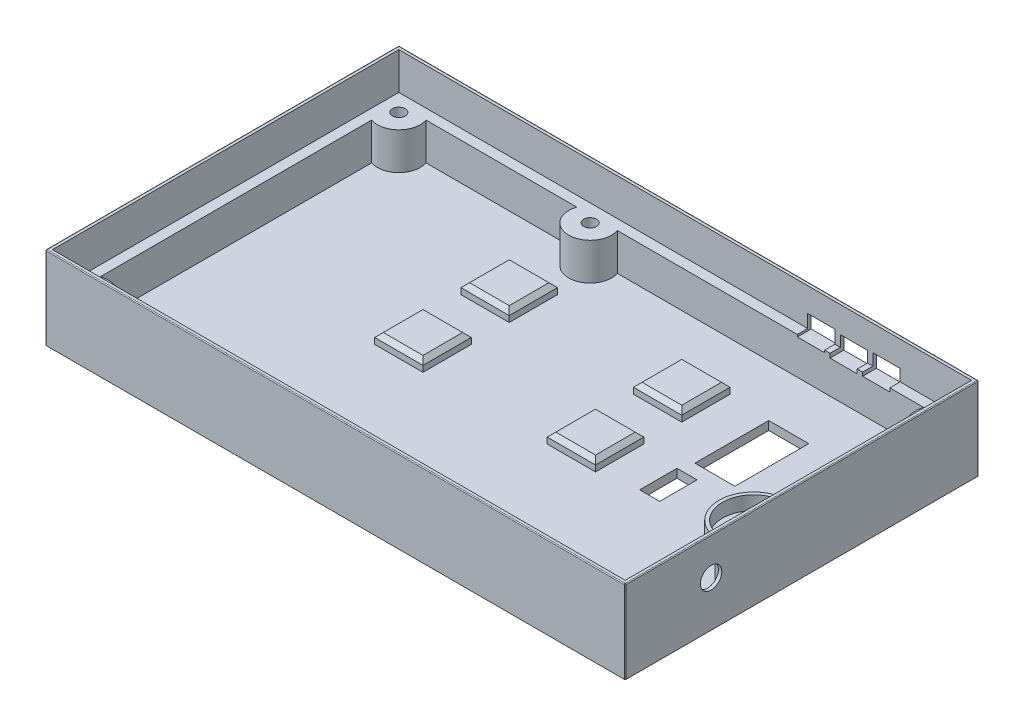
SolidWorks part; units mm, degrees
ref_plane "Front Plane" through (0, 0, 0) normal (0, 0, 1) x (1, 0, 0)
ref_plane "Top Plane" through (0, 0, 0) normal (0, 1, 0) x (1, 0, 0)
ref_plane "Right Plane" through (0, 0, 0) normal (1, 0, 0) x (0, 0, -1)
sketch "BaseSketch1" plane through (0, 0, 0) normal (0, 1, 0) x (1, 0, 0)
  line L1 (0, 0) -> (168, 0)
  line L2 (0, 0) -> (0, 102.4)
  line L3 (0, 102.4) -> (168, 102.4)
  line L4 (168, 0) -> (168, 102.4)
  line L5 (126.2, 83.4) -> (137.8, 83.4)
  line L6 (126.2, 83.4) -> (126.2, 62)
  line L7 (126.2, 62) -> (137.8, 62)
  line L8 (137.8, 83.4) -> (137.8, 62)
  line L9 (124.9, 47.31) -> (130.7, 47.31)
  line L10 (124.9, 47.31) -> (124.9, 58.11)
  line L11 (124.9, 58.11) -> (130.7, 58.11)
  line L12 (130.7, 47.31) -> (130.7, 58.11)
  circle A0 centre (57, 77.4) radius 2
  circle A1 centre (107, 77.4) radius 2
  circle A2 centre (57, 52.4) radius 2
  circle A3 centre (107, 52.4) radius 2
  circle A4 centre (6, 96.4) radius 1.85
  circle A5 centre (6, 6) radius 1.85
  circle A6 centre (162, 6) radius 1.85
  circle A7 centre (162, 96.4) radius 1.85
  circle A8 centre (61.45, 96.4) radius 1.85
  dimension "D16" = 3.7
  dimension "D7" = 4
  dimension "D1" = 102.4
  dimension "D2" = 168
  dimension "D3" = 50
  dimension "D4" = 25
  dimension "D6" = 25
  dimension "D8" = 21.4
  dimension "D9" = 11.6
  dimension "D10" = 40.4
  dimension "D12" = 5.8
  dimension "D13" = 10.8
  dimension "D15" = 55.09
  dimension "D17" = 6
  dimension "D18" = 6
  dimension "D19" = 6
  dimension "D20" = 6
  dimension "D5" = 57
  dimension "D11" = 41.8
  dimension "D14" = 43.1
  dimension "D21" = 106.55
extrude "BaseBoss-Extrude1" add sketch "BaseSketch1" along normal blind 2.5
sketch "Sketch2" plane through (0, 2.5, 0) normal (0, 1, 0) x (1, 0, 0)
  line L1 (0, 0) -> (168, 0)
  line L2 (0, 0) -> (0, 102.4)
  line L3 (0, 102.4) -> (168, 102.4)
  line L4 (168, 0) -> (168, 102.4)
  line L5 (4, 98.4) -> (164, 98.4)
  line L6 (4, 98.4) -> (4, 4)
  line L7 (4, 4) -> (164, 4)
  line L8 (164, 98.4) -> (164, 4)
  dimension "D1" = 4
  dimension "D2" = 4
  dimension "D3" = 4
  dimension "D4" = 4
extrude "WallBoss-Extrude2" add sketch "Sketch2" along normal blind 21.5
sketch "Sketch3" plane through (0, 2.5, 0) normal (0, 1, 0) x (1, 0, 0)
  line L1 (50, 84.4) -> (64, 84.4)
  line L2 (50, 84.4) -> (50, 70.4)
  line L3 (50, 70.4) -> (64, 70.4)
  line L4 (64, 84.4) -> (64, 70.4)
  line L5 (50, 84.4) -> (64, 70.4) construction
  line L6 (50, 70.4) -> (64, 84.4) construction
  line L7 (50, 59.4) -> (64, 59.4)
  line L8 (50, 59.4) -> (50, 45.4)
  line L9 (50, 45.4) -> (64, 45.4)
  line L10 (64, 59.4) -> (64, 45.4)
  line L11 (50, 59.4) -> (64, 45.4) construction
  line L12 (50, 45.4) -> (64, 59.4) construction
  line L13 (100, 84.4) -> (114, 84.4)
  line L14 (100, 84.4) -> (100, 70.4)
  line L15 (100, 70.4) -> (114, 70.4)
  line L16 (114, 84.4) -> (114, 70.4)
  line L17 (100, 84.4) -> (114, 70.4) construction
  line L18 (100, 70.4) -> (114, 84.4) construction
  line L19 (100, 59.4) -> (114, 59.4)
  line L20 (100, 59.4) -> (100, 45.4)
  line L21 (100, 45.4) -> (114, 45.4)
  line L22 (114, 59.4) -> (114, 45.4)
  line L23 (100, 59.4) -> (114, 45.4) construction
  line L24 (100, 45.4) -> (114, 59.4) construction
  point P0 (57, 77.4)
  point P6 (57, 52.4)
  point P12 (107, 77.4)
  point P18 (107, 52.4)
  dimension "D1" = 14
extrude "MountHoleBoss-Extrude3" add sketch "Sketch3" along normal blind 3
chamfer "MountHoleBossChamfer3" distance 1.25 angle 45 16 edges at (57, 5.5, -59.4) (107, 5.5, -59.4) (107, 5.5, -84.4) (57, 5.5, -84.4) (50, 5.5, -52.4) (100, 5.5, -52.4) (100, 5.5, -77.4) (50, 5.5, -77.4) (64, 5.5, -52.4) (114, 5.5, -52.4) (114, 5.5, -77.4) (64, 5.5, -77.4) (57, 5.5, -70.4) (57, 5.5, -45.4) (107, 5.5, -45.4) (107, 5.5, -70.4)
sketch "HDMI7MountHolesSketch8" plane through (0, 2.5, 0) normal (0, 1, 0) x (1, 0, 0)
  line L0 (164, 98.4) -> (4, 98.4) construction
  line L1 (4, 98.4) -> (4, 4) construction
  line L2 (4, 90.5243) -> (4, 98.4)
  line L3 (4, 98.4) -> (11.8757, 98.4)
  line L4 (164, 4) -> (164, 98.4) construction
  line L5 (4, 4) -> (164, 4) construction
  line L6 (4, 98.4) -> (4, 4) construction
  line L7 (4, 4) -> (164, 4) construction
  line L8 (156.1243, 98.4) -> (164, 98.4)
  line L9 (164, 98.4) -> (164, 90.5243)
  line L10 (156.1243, 4) -> (164, 4)
  line L11 (164, 4) -> (164, 11.8757)
  line L12 (11.8757, 4) -> (4, 4)
  line L13 (4, 4) -> (4, 11.8757)
  line L14 (55.5743, 98.4) -> (67.3257, 98.4)
  arc A0 (11.8757, 98.4) -> (4, 90.5243) centre (6, 96.4) cw
  circle A1 centre (6, 96.4) radius 1.85
  circle A2 centre (6, 96.4) radius 1.85 construction
  circle A3 centre (162, 96.4) radius 1.85
  circle A4 centre (162, 96.4) radius 1.85 construction
  arc A5 (164, 90.5243) -> (156.1243, 98.4) centre (162, 96.4) cw
  arc A6 (164, 11.8757) -> (156.1243, 4) centre (162, 6) ccw
  arc A7 (4, 11.8757) -> (11.8757, 4) centre (6, 6) cw
  circle A8 centre (162, 6) radius 1.85
  circle A9 centre (162, 6) radius 1.85 construction
  circle A10 centre (6, 6) radius 1.85
  circle A11 centre (6, 6) radius 1.85 construction
  arc A12 (55.5743, 98.4) -> (67.3257, 98.4) centre (61.45, 96.4) ccw
  circle A13 centre (61.45, 96.4) radius 1.85
  circle A14 centre (61.45, 96.4) radius 1.85 construction
extrude "HDMI7MountHolesBoss-Extrude4" add sketch "HDMI7MountHolesSketch8" along normal blind 10.75
sketch "DisplayButtonsSketch9" plane through (0, 0, -102.4) normal (0, 0, -1) x (-1, 0, 0)
  line L0 (-168, 24) -> (0, 24) construction
  line L1 (-146.3, 16.61) -> (-138.4, 16.61)
  line L2 (-146.3, 16.61) -> (-146.3, 12.21)
  line L3 (-146.3, 12.21) -> (-138.4, 12.21)
  line L4 (-138.4, 16.61) -> (-138.4, 12.21)
  line L5 (-136.85, 16.4439) -> (-128.95, 16.4439)
  line L6 (-136.85, 16.4439) -> (-136.85, 12.0439)
  line L7 (-136.85, 12.0439) -> (-128.95, 12.0439)
  line L8 (-128.95, 16.4439) -> (-128.95, 12.0439)
  line L9 (-127.4, 17.0239) -> (-119.5, 17.0239)
  line L10 (-127.4, 17.0239) -> (-127.4, 12.6239)
  line L11 (-127.4, 12.6239) -> (-119.5, 12.6239)
  line L12 (-119.5, 17.0239) -> (-119.5, 12.6239)
  line L13 (-168, 24) -> (-168, 0) construction
  dimension "D1" = 7.9
  dimension "D3" = 11.79
  dimension "D4" = 29.6
  dimension "D2" = 4.4
  dimension "D6" = 1.55
  dimension "D5" = 1.55
  dimension "D7" = 48.5
  dimension "D8" = 7.9
  dimension "D9" = 7.9
extrude "DisplayButtonsCut-Extrude1" cut sketch "DisplayButtonsSketch9" against normal up to next
sketch "AudioConnectorSketch10" plane through (168, 0, 0) normal (1, 0, 0) x (0, 0, -1)
  line L0 (0, 24) -> (102.4, 24) construction
  line L1 (0, 24) -> (0, 0) construction
  circle A0 centre (24.9, 13.2) radius 3.1
  dimension "D1" = 6.2
  dimension "D2" = 10.8
  dimension "D3" = 24.9
extrude "AudioConnectorCut-Extrude2" cut sketch "AudioConnectorSketch10" against normal up to next
sketch "M3BoreSketch11" plane through (0, 0, 0) normal (0, -1, 0) x (1, 0, 0)
  circle A0 centre (6, -6) radius 2.85
  circle A1 centre (162, -6) radius 2.85
  circle A2 centre (162, -96.4) radius 2.85
  circle A3 centre (6, -96.4) radius 2.85
  circle A4 centre (61.45, -96.4) radius 2.85
  dimension "D1" = 5.7
extrude "M3BoreCut-Extrude3" cut sketch "M3BoreSketch11" against normal blind 3
sketch "UpperThinWallSketch4" plane through (0, 24, 0) normal (0, 1, 0) x (1, 0, 0)
  line L1 (4, 98.4) -> (164, 98.4)
  line L2 (4, 98.4) -> (4, 4)
  line L3 (4, 4) -> (164, 4)
  line L4 (164, 98.4) -> (164, 4)
  line L6 (167, 1) -> (1, 1)
  line L7 (167, 1) -> (167, 101.4)
  line L8 (167, 101.4) -> (1, 101.4)
  line L9 (1, 1) -> (1, 101.4)
  dimension "D1" = 3
  dimension "D2" = 3
  dimension "D3" = 3
  dimension "D4" = 3
extrude "UpperThinWallCut-Extrude1" cut sketch "UpperThinWallSketch4" against normal blind 10.75
sketch "HDMI7AudioConnectorKnotchSketch5" plane through (0, 13.25, 0) normal (0, 1, 0) x (1, 0, 0)
  line L0 (164, 27.9996) -> (167, 27.9996) construction
  line L1 (164, 29.9996) -> (167, 29.9996)
  line L2 (164, 29.9996) -> (164, 19.8004)
  line L3 (164, 19.8004) -> (167, 19.8004)
  line L4 (167, 29.9996) -> (167, 19.8004)
  line L6 (167, 1) -> (167, 21.8004) construction
  line L7 (164, 11.8757) -> (164, 90.5243) construction
  line L8 (167, 21.8004) -> (164, 21.8004) construction
  dimension "D1" = 2
  dimension "D2" = 2
extrude "HDMI7AudioConnectorKnotchCut-Extrude2" cut sketch "HDMI7AudioConnectorKnotchSketch5" against normal blind 8.2
fillet "TopFillet1" radius 0.25 4 edges at (168, 24, -51.2) (84, 24, 0) (0, 24, -51.2) (84, 24, -102.4)
fillet "CornerFillet2" radius 0.25 8 edges at (0.0732, 23.9268, -0.0732) (0.0732, 23.9268, -102.3268) (167.9268, 23.9268, -0.0732) (0, 11.875, 0) (0, 11.875, -102.4) (168, 11.875, 0) (167.9268, 23.9268, -102.3268) (168, 11.875, -102.4)
sketch "SpeakerHoleSketch4" plane through (0, 2.5, 0) normal (0, 1, 0) x (1, 0, 0)
  line L0 (0.25, 102.4) -> (167.75, 102.4) construction
  line L1 (168, 102.15) -> (168, 0.25) construction
  circle A0 centre (153, 52.2) radius 6.75
  dimension "D1" = 13.5
  dimension "D2" = 50.2
  dimension "D3" = 15
extrude "SpeaerHoleCut-Extrude1" cut sketch "SpeakerHoleSketch4" against normal through all
sketch "SpeakerHolderSketch5" plane through (0, 2.5, 0) normal (0, 1, 0) x (1, 0, 0)
  line L2 (50, 59.4) -> (50, 45.4) construction
  line L3 (50, 45.4) -> (64, 45.4) construction
  circle A0 centre (153, 52.2) radius 9
  circle A1 centre (153, 52.2) radius 10
  point P4 (0, 0)
  point P12 (153.2499, 42.2)
  point P13 (153.2517, 43.2)
  dimension "D1" = 18
  dimension "D2" = 20
extrude "SpeakerHolderBoss-Extrude1" add sketch "SpeakerHolderSketch5" along normal blind 4
equation "\"HDMI7CaseWidth\"= 100mm + .4mm'Spec Add .4mm as width was slightly to tight"
equation "\"D1@BaseSketch1\" = \"HDMI7CaseWidth\" + \"HDMI7OuterCaseWallThickness\" * 2"
equation "\"HDMI7CaseLength\"= 165mm + 1mm'Spec Add 1mm as length did not fit"
equation "\"HDMI7CaseHeight\"= 24mm"
equation "\"HDMI7Height\"= 10.75mm'Spec"
equation "\"HDMI7MountingHoleOffset\"= 5mm'Spec"
equation "\"M3ScrewDiameter\"= 3mm + .5'Spec Add .5mm for easy screw insert"
equation "\"D2@BaseSketch1\"= \"HDMI7CaseLength\" + \"HDMI7OuterCaseWallThickness\" * 2"
equation "\"HDMI7BaseThickness\"= 2.5mm"
equation "\"HDMIMountHoleXDistance\"=50"
equation "\"D3@BaseSketch1\"=\"HDMIMountHoleXDistance\""
equation "\"HDMIMountHoleYDistance\"=25"
equation "\"D10@BaseSketch1\"=\"HDMI7HDMIConnectorDistanceFromTop\" + \"HDMI7OuterCaseWallThickness\" + \"HDMI7SpaceAroundAConnector\""
equation "\"D6@BaseSketch1\" = \"HDMI7MountingBracketOffsetFromTop\" + \"HDMI7OuterCaseWallThickness\""
equation "\"D15@BaseSketch1\"=\"HDMI7USBCConnectorDistanceFromTop\" + \"HDMI7OuterCaseWallThickness\" + \"HDMI7SpaceAroundAConnector\"*2"
equation "\"D1@BaseBoss-Extrude1\" = \"HDMI7BaseThickness\""
equation "\"D1@Sketch2\"=\"HDMI7OuterCaseWallThickness\" + \"HDMI7InnerCaseWallThickness\""
equation "\"D2@Sketch2\"=\"HDMI7OuterCaseWallThickness\" + \"HDMI7InnerCaseWallThickness\""
equation "\"D3@Sketch2\"=\"HDMI7OuterCaseWallThickness\" +\"HDMI7InnerCaseWallThickness\""
equation "\"D4@Sketch2\"=\"HDMI7OuterCaseWallThickness\" + \"HDMI7InnerCaseWallThickness\""
equation "\"D1@WallBoss-Extrude2\" = \"HDMI7CaseHeight\" - \"HDMI7BaseThickness\""
equation "\"D1@Sketch3\"=\"M3ScrewDiameter\"*4"
equation "\"D1@MountHoleBoss-Extrude3\"=\"M3ButtonHeadLength\""
equation "\"D16@BaseSketch1\"=\"M3ScrewDiameter\" +.2"
equation "\"D18@BaseSketch1\"=\"HDMI7MountingHoleOffset\" + \"HDMI7OuterCaseWallThickness\""
equation "\"D17@BaseSketch1\"=\"HDMI7MountingHoleOffset\"+\"HDMI7OuterCaseWallThickness\""
equation "\"D19@BaseSketch1\"=\"HDMI7MountingHoleOffset\"+\"HDMI7OuterCaseWallThickness\""
equation "\"D20@BaseSketch1\"=\"HDMI7MountingHoleOffset\"+\"HDMI7OuterCaseWallThickness\""
equation "\"D1@HDMI7MountHolesBoss-Extrude4\"=\"HDMI7CaseHeight\" - \"HDMI7Height\" - \"HDMI7BaseThickness\""
equation "\"D5@BaseSketch1\" = \"HDMI7MountingBracketOffsetFromEdge\" + \"HDMI7OuterCaseWallThickness\""
equation "\"D4@DisplayButtonsSketch9\"=\"HDMI7DisplayButtonDistanceFromNearestEdge\" + \"HDMI7OuterCaseWallThickness\" + \"HDMI7SpaceAroundAConnector\""
equation "\"D2@AudioConnectorSketch10\"= \"HDMI7AudioConnectorDistanceFromTop\" - \"HDMI7AudioConnectorHoleDiameter\" / 2"
equation "\"D3@AudioConnectorSketch10\"= \"HDMI7AudioConnectorDistanceFromNearestEdge\" + \"HDMI7OuterCaseWallThickness\" - \"HDMI7AudioConnectorHoleDiameter\" / 2"
equation "\"M3ButtonHeadDiameter\"= 5.5mm'Spec"
equation "\"M3ButtonHeadLength\"= 3mm'Spec"
equation "\"D1@M3BoreSketch11\"=\"M3ButtonHeadDiameter\" + .2mm"
equation "\"D1@M3BoreCut-Extrude3\"=\"M3ButtonHeadLength\""
equation "\"HDMI7InnerCaseWallThickness\"= 3mm"
equation "\"HDMI7OuterCaseWallThickness\"= 1mm"
equation "\"D1@UpperThinWallSketch4\" = \"HDMI7InnerCaseWallThickness\""
equation "\"D2@UpperThinWallSketch4\" = \"HDMI7InnerCaseWallThickness\""
equation "\"D3@UpperThinWallSketch4\" = \"HDMI7InnerCaseWallThickness\""
equation "\"D4@UpperThinWallSketch4\" = \"HDMI7InnerCaseWallThickness\""
equation "\"D1@UpperThinWallCut-Extrude1\" = \"HDMI7Height\""
equation "\"HDMI7AudioConnectorHoleDiameter\"= 6mm + \"HDMI7SpaceAroundAConnector\" * 2"
equation "\"D1@AudioConnectorSketch10\"=\"HDMI7AudioConnectorHoleDiameter\""
equation "\"HDMI7AudioConnectorDistanceFromNearestEdge\"= 27mm"
equation "\"HDMI7AudioConnectorDistanceFromTop\"= 13.8mm + \"HDMI7SpaceAroundAConnector\""
equation "\"D1@HDMI7AudioConnectorKnotchCut-Extrude2\"=\"HDMI7AudioConnectorHoleDiameter\" + 2mm"
equation "\"HDMI7DisplayButtonDistanceFromTop\"=11.69"
equation "\"D3@DisplayButtonsSketch9\"=\"HDMI7DisplayButtonDistanceFromTop\" + \"HDMI7SpaceAroundAConnector\""
equation "\"HDMI7DisplayButtonHeight\"= 4.2mm"
equation "\"D2@DisplayButtonsSketch9\"=\"HDMI7DisplayButtonHeight\" + \"HDMI7SpaceAroundAConnector\"*2"
equation "\"HDMI7DisplayButtonWidth\"= 7.7mm"
equation "\"D1@DisplayButtonsSketch9\"=\"HDMI7DisplayButtonWidth\" + \"HDMI7SpaceAroundAConnector\" * 2"
equation "\"HDMI7DisplayButtonDistanceFromNearestEdge\"= 28.5mm"
equation "\"HDMI7DisplayButtonOffsetBetweenEach\"=1.75"
equation "\"D6@DisplayButtonsSketch9\"=\"HDMI7DisplayButtonOffsetBetweenEach\" - \"HDMI7SpaceAroundAConnector\"*2"
equation "\"D5@DisplayButtonsSketch9\"=\"HDMI7DisplayButtonOffsetBetweenEach\" - \"HDMI7SpaceAroundAConnector\"*2"
equation "\"HDMI7HDMIConnectorLength\"= 21.2mm'Measured"
equation "\"D8@BaseSketch1\"=\"HDMI7HDMIConnectorLength\" + \"HDMI7SpaceAroundAConnector\"*2"
equation "\"HDMI7HDMIConnectorWidth\"= 11.5mm'Measured"
equation "\"D9@BaseSketch1\"=\"HDMI7HDMIConnectorWidth\" + \"HDMI7SpaceAroundAConnector\""
equation "\"HDMI7USBConnectorLength\"= 10.7mm'Measured"
equation "\"D13@BaseSketch1\"=\"HDMI7USBConnectorLength\" + \"HDMI7SpaceAroundAConnector\""
equation "\"HDMI7USBCConnectorWidth\"= 5.7mm'Measured"
equation "\"D12@BaseSketch1\"=\"HDMI7USBCConnectorWidth\" + \"HDMI7SpaceAroundAConnector\""
equation "\"HDMI7HDMIConnectorDistanceFromNearestSide\"= 38.7mm"
equation "\"HDMI7USBConnectorDistanceFromNearestSide\" = 40mm"
equation "\"D11@BaseSketch1\"=\"HDMI7HDMIConnectorDistanceFromNearestSide\" + \"HDMI7InnerCaseWallThickness\" + \"HDMI7SpaceAroundAConnector\""
equation "\"D14@BaseSketch1\"=\"HDMI7USBConnectorDistanceFromNearestSide\" +\"HDMI7InnerCaseWallThickness\" + \"HDMI7SpaceAroundAConnector\""
equation "\"HDMI7USBCConnectorDistanceFromTop\" = 53.89mm"
equation "\"HDMI7HDMIConnectorDistanceFromTop\"= 39.3mm"
equation "\"HDMI7MountingBracketOffsetFromEdge\"= 56mm"
equation "\"HDMI7MountingBracketOffsetFromTop\"= 24mm"
equation "\"HDMI7SpaceAroundAConnector\"= .1mm"
equation "\"D7@BaseSketch1\"= \"M3HeatInsertHoleDiameter\""
equation "\"D8@DisplayButtonsSketch9\"=\"HDMI7DisplayButtonWidth\" + \"HDMI7SpaceAroundAConnector\"*2"
equation "\"D9@DisplayButtonsSketch9\"=\"HDMI7DisplayButtonWidth\" + \"HDMI7SpaceAroundAConnector\"*2"
equation "\"HDMI7MidMouningHoleOffset\"=106.55"
equation "\"D21@BaseSketch1\"=\"HDMI7MidMouningHoleOffset\""
equation "\"M3HeatInsertHoleDiameter\"= 4mm'Spec"
equation "\"SpeakerHoleDiameter\" = 13.5mm"
equation "\"D2@SpeakerHoleSketch4\" = \"HDMI7CaseWidth\" / 2"
equation "\"SpeakerDistanceFromNearestEdge\" = 15mm"
equation "\"D3@SpeakerHoleSketch4\" = \"SpeakerDistanceFromNearestEdge\""
equation "\"SpeakerDiameter\"= 18mm'Spec"
equation "\"D1@SpeakerHolderSketch5\"=\"SpeakerDiameter\""
equation "\"D2@SpeakerHolderSketch5\"=\"SpeakerDiameter\" + 2mm"
equation "\"SpeakerDepth\"=4"
equation "\"D1@SpeakerHolderBoss-Extrude1\"=\"SpeakerDepth\""
